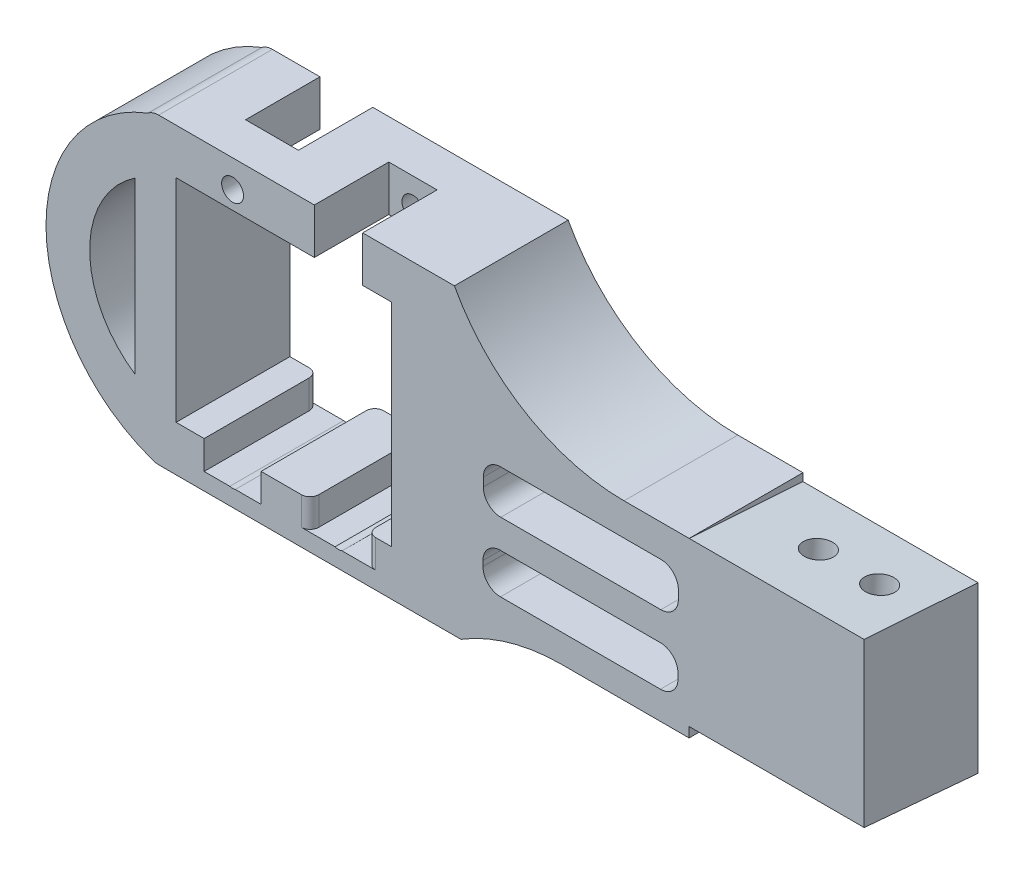
SolidWorks part; units mm, degrees
ref_plane "前视基准面" through (0, 0, 0) normal (0, 0, 1) x (1, 0, 0)
ref_plane "上视基准面" through (0, 0, 0) normal (0, 1, 0) x (1, 0, 0)
ref_plane "右视基准面" through (0, 0, 0) normal (1, 0, 0) x (0, 0, -1)
sketch "草图1" plane through (0, 0, 0) normal (0, 0, 1) x (1, 0, 0)
  line L0 (-3.601, 12.8247) -> (-3.601, 5.7079) construction
  line L1 (-9.851, 13.3747) -> (2.449, 13.3747) construction
  line L2 (-9.851, 13.3747) -> (-9.851, -10.8253) construction
  line L3 (-9.851, -10.8253) -> (2.449, -10.8253) construction
  line L4 (2.449, 13.3747) -> (2.449, -10.8253) construction
  line L5 (-9.851, 13.3747) -> (-22.151, 13.3747) construction
  line L6 (-9.851, 13.3747) -> (-9.851, -10.8253) construction
  line L7 (-9.851, -10.8253) -> (-22.151, -10.8253) construction
  line L8 (-22.151, 13.3747) -> (-22.151, -10.8253) construction
  line L9 (-15.701, 12.8247) -> (-15.701, 8.0194) construction
  line L10 (-24.7239, 15.4247) -> (5.2228, 15.4247) construction
  line L11 (-9.651, 1.2747) -> (-5.1019, 1.2747) construction
  line L12 (-24.1178, -12.8753) -> (3.6202, -12.8753) construction
  line L13 (-26.151, 18.5747) -> (-26.151, -16.0253)
  line L14 (-26.151, -16.0253) -> (6.449, -16.0253)
  line L15 (6.449, -16.0253) -> (6.449, 18.5747)
  line L16 (6.449, 18.5747) -> (-26.151, 18.5747)
  line L17 (-22.151, 13.3747) -> (-22.151, -10.8253)
  line L18 (-22.151, -10.8253) -> (2.449, -10.8253)
  line L19 (2.449, -10.8253) -> (2.449, 13.3747)
  line L20 (2.449, 13.3747) -> (-22.151, 13.3747)
  circle A0 centre (-15.701, 15.4247) radius 1.25
  circle A1 centre (-3.601, 15.4247) radius 1.25
  circle A2 centre (-15.701, -12.8753) radius 1.25
  circle A3 centre (-3.601, -12.8753) radius 1.25
  dimension "D6" = 2.5
  dimension "D7" = 4
  dimension "2" = 2.5
  dimension "D12" = 2.5
  dimension "D13" = 2.5
  dimension "D2" = 12.3
  dimension "D3" = 12.3
  dimension "D4" = 14.15
  dimension "D5" = 14.15
  dimension "D8" = 4
  dimension "D9" = 5.2
  dimension "D10" = 5.2
  dimension "D14" = 12.1
  dimension "1" = 12.1
extrude "凸台-拉伸1" add sketch "草图1" along normal blind 13
sketch "草图3" plane through (0, 0, 0) normal (0, 0, -1) x (-1, 0, 0)
  line L0 (15.701, -11.8253) -> (15.701, -6.7629) construction
  line L1 (22.151, -10.8253) -> (-2.449, -10.8253) construction
  line L2 (12.451, -7.5658) -> (18.951, -7.5658)
  line L3 (12.451, -7.5658) -> (12.451, -14.0848)
  line L4 (12.451, -14.0848) -> (18.951, -14.0848)
  line L5 (18.951, -7.5658) -> (18.951, -14.0848)
  line L6 (12.451, -7.5658) -> (18.951, -14.0848) construction
  line L7 (12.451, -14.0848) -> (18.951, -7.5658) construction
  point P1 (15.701, -10.8253)
  dimension "D1" = 6.5
extrude "切除-拉伸1" cut sketch "草图3" against normal blind 19
sketch "草图4" plane through (0, 0, 13) normal (0, 0, 1) x (1, 0, 0)
  line L0 (-3.601, -11.8253) -> (-3.601, -6.3141) construction
  line L1 (-22.151, -10.8253) -> (-18.951, -10.8253) construction
  line L2 (-6.851, -7.5915) -> (-0.351, -7.5915)
  line L3 (-6.851, -7.5915) -> (-6.851, -14.0591)
  line L4 (-6.851, -14.0591) -> (-0.351, -14.0591)
  line L5 (-0.351, -7.5915) -> (-0.351, -14.0591)
  line L6 (-6.851, -7.5915) -> (-0.351, -14.0591) construction
  line L7 (-6.851, -14.0591) -> (-0.351, -7.5915) construction
  point P1 (-3.601, -10.8253)
  dimension "D1" = 6.5
extrude "切除-拉伸2" cut sketch "草图4" against normal blind 23
sketch "草图5" plane through (6.449, 0, 0) normal (1, 0, 0) x (0, 0, -1)
  line L0 (-13.4, 18.0247) -> (-13.4, 22.7366) construction
  line L1 (-12.2184, 23.0074) -> (-11.5203, 26.9663) construction
  line L2 (0, 18.5747) -> (-6.1009, -16.0253) construction
  line L3 (0, -16.0253) -> (0, 18.5747) construction
  line L4 (-13, 18.5747) -> (0, 18.5747) construction
  line L5 (-13, -16.0253) -> (0, -16.0253) construction
  line L6 (-6.1009, -16.0253) -> (-13, -16.0253) construction
  line L7 (0, 18.5747) -> (-13, 18.5747) construction
  line L8 (-13, 18.5747) -> (-18.9169, -14.982) construction
  line L9 (-18.9169, -14.982) -> (-13, -16.0253) construction
  line L10 (-13, 18.5747) -> (9.0369, 14.689) construction
  line L11 (0.1283, -15.0502) -> (-24.5049, -10.7067) construction
  line L12 (-13, 18.5747) -> (-13, 10.0555)
  line L13 (-13, -16.0253) -> (-13, 18.5747) construction
  line L14 (-0.0781, -16.0253) -> (-21.5396, -16.0253) construction
  line L15 (-13, 10.0555) -> (-13, -1.2292) construction
  line L16 (-13, 18.5747) -> (0, 18.5747)
  line L17 (0, 16.2825) -> (0, -15.0276)
  line L18 (0, -15.0276) -> (0, -16.0253)
  line L19 (-13, 10.0555) -> (-13, -16.0253)
  line L20 (-13, -16.0253) -> (0, -16.0253)
  line L21 (0, 18.5747) -> (0, 16.2825)
  dimension "D1" = 10
  dimension "D2" = 90
  dimension "D3" = 0
extrude "凸台-拉伸2" add sketch "草图5" along normal blind 50
sketch "草图6" plane through (0, 0, 13) normal (0, 0, 1) x (1, 0, 0)
  line L0 (56.449, 18.5747) -> (56.449, -16.0253) construction
  line L1 (46.449, 3.7068) -> (56.449, 3.7068)
  line L2 (46.449, 3.7068) -> (46.449, -11.2932)
  line L3 (46.449, -11.2932) -> (56.449, -11.2932)
  line L4 (56.449, 3.7068) -> (56.449, -11.2932)
  line L5 (46.449, 3.7068) -> (56.449, -11.2932) construction
  line L6 (46.449, -11.2932) -> (56.449, 3.7068) construction
  point P0 (51.449, -3.7932)
  point P5 (56.449, 1.2747)
  dimension "D1" = 10
  dimension "D2" = 15
  dimension "D3" = 0
sketch "1" plane through (0, 0, 13) normal (0, 0, 1) x (1, 0, 0)
  line L0 (12.8989, -4.9643) -> (35.1755, -4.9643)
  line L1 (12.9369, 3.3053) -> (35.2199, 3.3053)
  line L2 (12.9369, 3.3053) -> (12.9369, -1.6722)
  line L3 (12.9369, -1.6722) -> (35.2199, -1.6722)
  line L4 (35.2199, 3.3053) -> (35.2199, -1.6722)
  line L5 (12.8989, -4.9643) -> (12.8989, -9.5629)
  line L6 (12.8989, -9.5629) -> (35.1755, -9.5629)
  line L7 (35.1755, -4.9643) -> (35.1755, -9.5629)
extrude "切除-拉伸5" cut sketch "1" against normal blind 34
fillet "圆角1" radius 2 8 edges at (35.1755, -9.5629, 6.5) (12.8989, -9.5629, 6.5) (12.8989, -4.9643, 6.5) (35.1755, -4.9643, 6.5) (35.2199, -1.6722, 6.5) (12.9369, -1.6722, 6.5) (12.9369, 3.3053, 6.5) (35.2199, 3.3053, 6.5)
fillet "圆角2" radius 2 2 edges at (-26.151, -16.0253, 6.5) (-26.151, 18.5747, 6.5)
fillet "圆角5" radius 1 4 edges at (-0.351, -12.4422, 13) (-6.851, -12.4422, 13) (-18.951, -12.455, 0) (-12.451, -12.455, 0)
sketch "草图9" plane through (0, 0, 0) normal (0, 0, -1) x (-1, 0, 0)
  line L1 (-64.2317, 25.1073) -> (-9.6367, 25.1073)
  line L2 (-64.2317, 25.1073) -> (-64.2317, 6.9954)
  line L3 (-64.2317, 6.9954) -> (-9.6367, 6.9954)
  line L4 (-9.6367, 25.1073) -> (-9.6367, 6.9954)
  line L5 (-62.9206, -12.7526) -> (-10.3858, -12.7526)
  line L6 (-62.9206, -12.7526) -> (-62.9206, -25.7419)
  line L7 (-62.9206, -25.7419) -> (-10.3858, -25.7419)
  line L8 (-10.3858, -12.7526) -> (-10.3858, -25.7419)
extrude "切除-拉伸6" cut sketch "草图9" against normal blind 41
fillet "圆角6" radius 22 2 edges at (9.6367, 6.9954, 6.5) (10.3858, -12.7526, 6.5)
sketch "草图12" plane through (0, 0, 0) normal (0, 0, -1) x (-1, 0, 0)
  line L0 (24.151, 18.5747) -> (24.4967, -15.9952)
  line L1 (24.3249, 1.2899) -> (43.8676, 1.2899) construction
  line L2 (26.8227, 1.2899) -> (26.8227, -8.4317)
  line L3 (26.4516, 11.0116) -> (28.7609, 11.0116) construction
  line L4 (26.4516, 11.0116) -> (26.4516, -8.4317) construction
  line L5 (26.4516, -8.4317) -> (28.7609, -8.4317) construction
  line L6 (28.7609, 11.0116) -> (28.7609, -8.4317) construction
  line L7 (26.4516, 11.0116) -> (28.7609, -8.4317) construction
  line L8 (26.4516, -8.4317) -> (28.7609, 11.0116) construction
  line L9 (26.8227, 1.2899) -> (26.8227, 11.0116)
  arc A0 (24.151, 18.5747) -> (24.4967, -15.9952) centre (18.8996, 1.2355) cw
  arc A1 (24.151, -16.0253) -> (26.151, -14.0253) centre (24.151, -14.0253) ccw construction
  arc A2 (26.8227, 11.0116) -> (26.8227, -8.4317) centre (20.3469, 1.2899) cw
  point P8 (27.6062, 1.2899)
extrude "凸台-拉伸4" add sketch "草图12" against normal up to surface (13 mm away) up to face at (8.0606, -0.5738, 13)
sketch "草图13" plane through (0, 0, 13) normal (0, 0, 1) x (1, 0, 0)
  line L1 (-6.3604, 19.6056) -> (-0.8415, 19.6056)
  line L2 (-6.3604, 19.6056) -> (-6.3604, 11.2438)
  line L3 (-6.3604, 11.2438) -> (-0.8415, 11.2438)
  line L4 (-0.8415, 19.6056) -> (-0.8415, 11.2438)
  line L5 (-6.3604, 19.6056) -> (-0.8415, 11.2438) construction
  line L6 (-6.3604, 11.2438) -> (-0.8415, 19.6056) construction
  point P0 (-3.601, 15.4247)
extrude "切除-拉伸8" cut sketch "草图13" against normal blind 8.5
sketch "草图14" plane through (0, 0, 0) normal (0, 0, -1) x (-1, 0, 0)
  line L1 (12.6817, 19.2953) -> (18.7203, 19.2953)
  line L2 (12.6817, 19.2953) -> (12.6817, 11.5541)
  line L3 (12.6817, 11.5541) -> (18.7203, 11.5541)
  line L4 (18.7203, 19.2953) -> (18.7203, 11.5541)
  line L5 (12.6817, 19.2953) -> (18.7203, 11.5541) construction
  line L6 (12.6817, 11.5541) -> (18.7203, 19.2953) construction
  point P0 (15.701, 15.4247)
  dimension "D1" = 6.0387
extrude "切除-拉伸9" cut sketch "草图14" against normal blind 8.5
sketch "草图15" plane through (56.449, 0, 0) normal (1, 0, 0) x (0, 0, -1)
  line L0 (-13, 6.9954) -> (6.0232, 5.7077)
  line L1 (6.0232, 5.7077) -> (0, -12.7526)
  line L2 (0, -12.7526) -> (-13, -11.6152)
  line L3 (-13, 10.0555) -> (-13, -16.0253) construction
  line L4 (-13, -11.6152) -> (-13, 6.9954)
  line L5 (0, 6.9954) -> (-13, 6.9954) construction
  line L6 (0, -12.7526) -> (-13, -12.7526) construction
  dimension "D1" = 3.872
  dimension "D2" = 5
extrude "切除-拉伸11" cut sketch "草图15" against normal blind 20 flip side to cut
sketch "草图20" plane through (0, 6.0875, -0.412) normal (0, 0.9977, -0.0675) x (1, 0, 0)
  line L0 (41.8626, -6.663) -> (48.8626, -6.663) construction
  line L1 (56.449, -0.413) -> (36.449, -0.413) construction
  line L3 (56.449, -0.413) -> (56.449, -13.4427) construction
  circle A0 centre (44.449, -6.663) radius 1.625
  circle A1 centre (51.449, -6.663) radius 1.625
  dimension "D1" = 7
  dimension "D2" = 6.25
  dimension "D3" = 5
extrude "切除-拉伸15" cut sketch "草图20" against normal blind 40
sketch "草图21" plane through (56.449, 0, 0) normal (1, 0, 0) x (0, 0, -1)
  line L1 (0, 6.1154) -> (-13, 6.9954) construction
  line L2 (-13, -11.6152) -> (0, -12.7526) construction
  line L3 (-5.0352, 6.4563) -> (-6.2981, -12.2015) construction
  dimension "D1" = 90
  dimension "D2" = 18.7005
